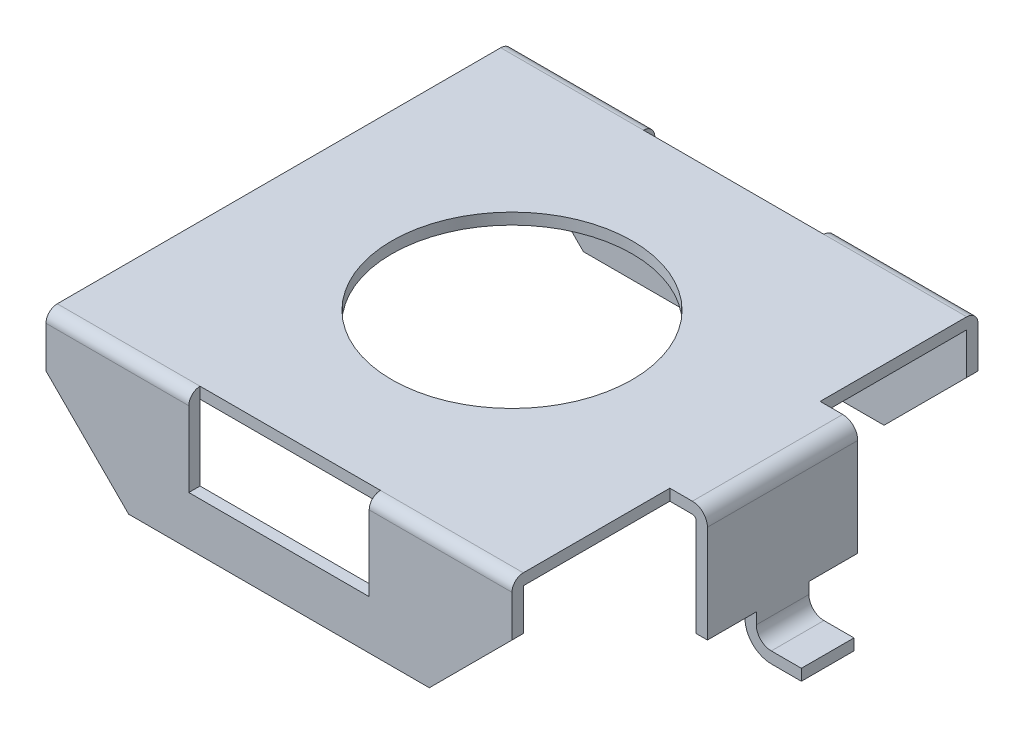
SolidWorks part; units mm, degrees
ref_plane "Front Plane" through (0, 0, 0) normal (0, 0, 1) x (1, 0, 0)
ref_plane "Top Plane" through (0, 0, 0) normal (0, 1, 0) x (1, 0, 0)
ref_plane "Right Plane" through (0, 0, 0) normal (1, 0, 0) x (0, 0, -1)
sketch "Sketch1" plane through (0, 0, 0) normal (1, 0, 0) x (0, 0, -1)
  line L0 (-3.1, 0.2) -> (-3.1, 2)
  line L1 (-3.1, 2) -> (3.1, 2)
  line L2 (3.1, 2) -> (3.1, 0.2)
  line L3 (3.41, 0) -> (-3.41, 0) construction
  line L4 (0, 0.99) -> (0, -0.99) construction
  dimension "D1" = 2
  dimension "D2" = 6.2
  dimension "D3" = 3.1
  dimension "D4" = 1.8
extrude "Extrude-Thin3" add sketch "Sketch1" along normal mid plane 6.2 thin thin type one direction wall 0.15
sketch "Sketch2" plane through (0, 0, 0) normal (0, 0, 1) x (1, 0, 0)
  line L1 (-1.2, 1.85) -> (1.2, 1.85)
  line L2 (-1.2, 1.85) -> (-1.2, 0.85)
  line L3 (-1.2, 0.85) -> (1.2, 0.85)
  line L4 (1.2, 1.85) -> (1.2, 0.85)
  line L5 (-3.1, 1.3) -> (-2, 0.2)
  line L6 (3.1, 0.2) -> (3.1, 1.3)
  line L7 (3.1, 0.2) -> (-3.1, 0.2) construction
  line L8 (-2, 0.2) -> (-3.1, 0.2)
  line L9 (-3.1, 0.2) -> (-3.1, 1.3)
  line L10 (-3.1, 0.2) -> (-3.1, 2) construction
  line L11 (3.1, 1.3) -> (2, 0.2)
  line L12 (3.1, 0.2) -> (3.1, 2) construction
  line L13 (2, 0.2) -> (3.1, 0.2)
  line L14 (0, -0.99) -> (0, 0.99) construction
  dimension "D1" = 4
  dimension "D2" = 2
  dimension "D3" = 45
  dimension "D4" = 45
  dimension "D5" = 2.4
  dimension "D6" = 1.2
extrude "Cut-Extrude1" cut sketch "Sketch2" against normal through all and the other way through all
sketch "Sketch3" plane through (0, 2, 0) normal (0, 1, 0) x (1, 0, 0)
  line L1 (-1.2, 3.1) -> (1.2, 3.1)
  line L2 (-1.2, 3.1) -> (-1.2, 2.95)
  line L3 (-1.2, 2.95) -> (1.2, 2.95)
  line L4 (1.2, 3.1) -> (1.2, 2.95)
  line L5 (-1.2, -3.1) -> (1.2, -3.1)
  line L6 (-1.2, -3.1) -> (-1.2, -2.95)
  line L7 (-1.2, -2.95) -> (1.2, -2.95)
  line L8 (1.2, -3.1) -> (1.2, -2.95)
extrude "Cut-Extrude2" cut sketch "Sketch3" against normal blind 1
fillet "Fillet1" radius 0.15 4 edges at (-2.15, 2, -3.1) (2.15, 2, -3.1) (-2.15, 2, 3.1) (2.15, 2, 3.1)
sketch "Sketch4" plane through (0, 2, 0) normal (0, 1, 0) x (1, 0, 0)
  circle A0 centre (0, 0) radius 1.6
  dimension "D1" = 3.2
extrude "Cut-Extrude3" cut sketch "Sketch4" against normal blind 1
sketch "Sketch5" plane through (0, 0, 0) normal (0, 0, 1) x (1, 0, 0)
  line L0 (3.1, 2) -> (3.4, 2)
  line L1 (3.6, 1.8) -> (3.6, 0.35)
  line L2 (3.8, 0.15) -> (4.2, 0.15)
  line L3 (3.41, 0) -> (-3.41, 0) construction
  line L4 (0, -0.99) -> (0, 0.99) construction
  line L5 (3.1, 1.3) -> (3.1, 1.85) construction
  arc A0 (3.6, 0.35) -> (3.8, 0.15) centre (3.8, 0.35) ccw
  arc A1 (3.4, 2) -> (3.6, 1.8) centre (3.4, 1.8) cw
  point P9 (3.1, 1.575)
  dimension "D5" = 0.2
  dimension "D1" = 0.15
  dimension "D2" = 3.6
  dimension "D3" = 0.5
  dimension "D4" = 4.2
extrude "Extrude-Thin4" add sketch "Sketch5" along normal mid plane 2 thin thin type one direction wall 0.15
sketch "Sketch6" plane through (0, 0, 0) normal (0, -1, 0) x (1, 0, 0)
  line L1 (4.2, 1) -> (3.2, 1)
  line L2 (4.2, 1) -> (4.2, 0.35)
  line L3 (4.2, 0.35) -> (3.2, 0.35)
  line L4 (3.2, 1) -> (3.2, 0.35)
  line L5 (4.2, -1) -> (3.2, -1)
  line L6 (4.2, -1) -> (4.2, -0.35)
  line L7 (4.2, -0.35) -> (3.2, -0.35)
  line L8 (3.2, -1) -> (3.2, -0.35)
  dimension "D1" = 1
  dimension "D2" = 0.7
extrude "Cut-Extrude4" cut sketch "Sketch6" against normal blind 0.5
